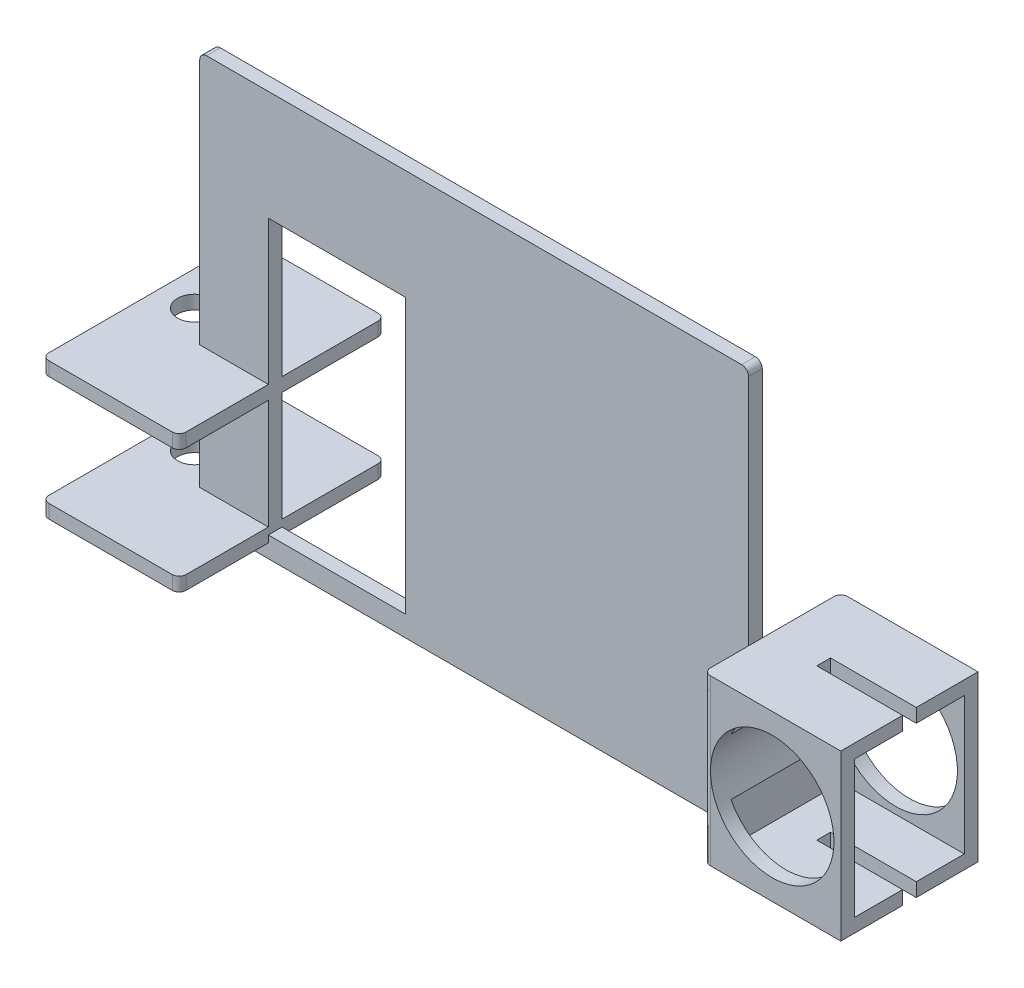
SolidWorks part; units mm, degrees
ref_plane "Front Plane" through (0, 0, 0) normal (0, 0, 1) x (1, 0, 0)
ref_plane "Top Plane" through (0, 0, 0) normal (0, 1, 0) x (1, 0, 0)
ref_plane "Right Plane" through (0, 0, 0) normal (1, 0, 0) x (0, 0, -1)
sketch "Sketch1" plane through (0, 0, 0) normal (0, 1, 0) x (1, 0, 0)
  line L0 (-2.2917, 11.0417) -> (-22.2917, 11.0417)
  line L1 (-22.2917, 11.0417) -> (-22.2917, -8.9583)
  line L2 (-22.2917, -8.9583) -> (-2.2917, -8.9583)
  line L3 (-20.2917, 9.0417) -> (-2.2917, 9.0417)
  line L4 (-20.2917, 9.0417) -> (-20.2917, -6.9583)
  line L5 (-20.2917, -6.9583) -> (-2.2917, -6.9583)
  line L6 (-2.2917, -6.9583) -> (-2.2917, -8.9583)
  line L7 (-2.2917, 9.0417) -> (-2.2917, 11.0417)
  dimension "D1" = 20
  dimension "D2" = 20
  dimension "D3" = 20
  dimension "D4" = 2
  dimension "D5" = 2
  dimension "D6" = 2
extrude "Boss-Extrude1" add sketch "Sketch1" along normal blind 20
fillet "Fillet1" radius 1 2 edges at (-22.2917, 10, -11.0417) (-22.2917, 10, 8.9583)
sketch "Sketch2" plane through (0, 0, 8.9583) normal (0, 0, 1) x (1, 0, 0)
  line L0 (-21.2917, 0) -> (-2.2917, 0) construction
  line L1 (-2.2917, 20) -> (-2.2917, 0) construction
  circle A0 centre (-12.2917, 10) radius 9
  dimension "D3" = 18
  dimension "D1" = 10
  dimension "D2" = 10
extrude "Cut-Extrude1" cut sketch "Sketch2" against normal blind 20
sketch "Sketch3" plane through (0, 20, 0) normal (0, 1, 0) x (1, 0, 0)
  line L0 (-21.2917, 11.0417) -> (-2.2917, 11.0417)
  line L1 (-2.2917, 11.0417) -> (-2.2917, -8.9583)
  line L2 (-2.2917, -8.9583) -> (-22.2917, -8.9583)
  line L3 (-22.2917, -8.9583) -> (-22.2917, 11.0417)
  line L4 (-22.2917, 11.0417) -> (-21.2917, 11.0417)
  line L9 (-2.2917, 2.3778) -> (-2.2917, 0.3778)
  line M10 (-2.2917, 11.0417) -> (-21.2917, 11.0417)
  arc M11 (-21.2917, 11.0417) -> (-22.2917, 10.0417) centre (-21.2917, 10.0417) ccw
  line M12 (-22.2917, 10.0417) -> (-22.2917, -7.9583)
  arc M13 (-22.2917, -7.9583) -> (-21.2917, -8.9583) centre (-21.2917, -7.9583) ccw
  line M14 (-21.2917, -8.9583) -> (-2.2917, -8.9583)
  line M15 (-2.2917, -8.9583) -> (-2.2917, -6.9583)
  line M16 (-2.2917, -6.9583) -> (-20.2917, -6.9583)
  line M17 (-20.2917, -6.9583) -> (-20.2917, 9.0417)
  line M18 (-20.2917, 9.0417) -> (-2.2917, 9.0417)
  line M19 (-2.2917, 9.0417) -> (-2.2917, 11.0417)
  dimension "D1" = 20
extrude "Boss-Extrude2" add sketch "Sketch3" along normal blind 2 contours L1 M18 M17 M16 | M19 M10 M11 M12 M13 M14 M15 M16 M17 M18 region at (-11.7917, 20, -10.7588) region at (-11.2917, 20, -1.0417)
sketch "Sketch4" plane through (0, 0, 0) normal (0, -1, 0) x (1, 0, 0)
  line L0 (-2.2917, 8.9583) -> (-2.2917, -11.0417)
  line L1 (-2.2917, -11.0417) -> (-22.2917, -11.0417)
  line L2 (-22.2917, -11.0417) -> (-22.2917, 8.9583)
  line L3 (-22.2917, 8.9583) -> (-2.2917, 8.9583)
  dimension "D1" = 20
  dimension "D2" = 20
extrude "Boss-Extrude3" add sketch "Sketch4" along normal blind 2
fillet "Fillet2" radius 1 2 edges at (-22.2917, -1, -11.0417) (-22.2917, -1, 8.9583)
sketch "Sketch5" plane through (0, 22, 0) normal (0, 1, 0) x (1, 0, 0)
  line L0 (-2.2917, 11.0417) -> (-2.2917, -8.9583) construction
  line L1 (-14.7917, 2.0417) -> (-2.2917, 2.0417)
  line L2 (-14.7917, 2.0417) -> (-14.7917, 0.0417)
  line L3 (-14.7917, 0.0417) -> (-2.2917, 0.0417)
  line L4 (-2.2917, 2.0417) -> (-2.2917, 0.0417)
  line L5 (-21.2917, -8.9583) -> (-2.2917, -8.9583) construction
  dimension "D1" = 12.5
  dimension "D2" = 2
  dimension "D3" = 9
extrude "Cut-Extrude2" cut sketch "Sketch5" against normal blind 24
sketch "Sketch6" plane through (-22.2917, 0, 0) normal (-1, 0, 0) x (0, 0, 1)
  line L0 (2.4083, -37) -> (0.4083, -37)
  line L5 (0.4083, -37) -> (0.4083, -2)
  line L6 (-10.0417, 22) -> (7.9583, 22) construction
  line L7 (2.4083, 22) -> (0.4083, 22)
  line L8 (2.4083, 22) -> (2.4083, -2)
  line L10 (0.4083, 22) -> (0.4083, -2)
  line L11 (7.9583, -2) -> (-10.0417, -2) construction
  line L13 (2.4083, -2) -> (2.4083, -37)
  line L14 (8.9583, 22) -> (8.9583, 10) construction
  point P6 (1.4083, -37)
  dimension "D1" = 6.55
  dimension "D2" = 2
  dimension "D3" = 35
extrude "Boss-Extrude4" add sketch "Sketch6" along normal blind 80
fillet "Fillet3" radius 1 3 edges at (-22.2917, -37, 1.4083) (-102.2917, -37, 1.4083) (-102.2917, 22, 1.4083)
sketch "Sketch8" plane through (0, 0, 0.4083) normal (0, 0, -1) x (-1, 0, 0)
  line L0 (82.2917, 22) -> (82.2917, -40.0805) construction
  line L1 (72.2917, 19) -> (92.2917, 19)
  line L2 (72.2917, 19) -> (72.2917, -21)
  line L3 (72.2917, -21) -> (92.2917, -21)
  line L4 (92.2917, 19) -> (92.2917, -21)
  line L5 (101.2917, 22) -> (22.2917, 22) construction
  line L6 (12.2917, 10) -> (131.172, 10) construction
  circle A0 centre (12.2917, 10) radius 9 construction
  circle A1 centre (12.2917, 10) radius 7.1139
  dimension "D4" = 70
  dimension "D1" = 20
  dimension "D2" = 40
  dimension "D3" = 10
  dimension "D5" = 9
extrude "Cut-Extrude3" cut sketch "Sketch8" against normal blind 2
sketch "Sketch9" plane through (0, 0, 0.4083) normal (0, 0, -1) x (-1, 0, 0)
  line L0 (92.471, 20) -> (102.2917, 20)
  line L1 (102.2917, 21) -> (102.2917, -36) construction
  line L3 (102.2917, 18) -> (92.2917, 18)
  line L4 (92.2917, -21) -> (92.2917, 19) construction
  line L5 (92.471, 20) -> (92.2917, 20)
  line L6 (92.2917, 20) -> (92.2917, 18)
  line L7 (92.2917, 2) -> (112.2917, 2)
  line L8 (112.2917, 2) -> (112.2917, 0)
  line L9 (112.2917, 0) -> (92.2917, 0)
  line L10 (92.2917, 0) -> (92.2917, 2)
  line L11 (102.2917, 20) -> (112.2917, 20)
  line L12 (112.2917, 20) -> (112.2917, 18)
  line L13 (112.2917, 18) -> (102.2917, 18)
  line L14 (101.2917, 22) -> (22.2917, 22) construction
  point P11 (97.2917, 18)
  dimension "D1" = 2
  dimension "D2" = 2
  dimension "D3" = 16
  dimension "D4" = 20
  dimension "D5" = 20
  dimension "D6" = 2
extrude "Boss-Extrude5" add sketch "Sketch9" along normal mid plane 30
fillet "Fillet4" radius 1 8 edges at (-112.2917, 19, -14.5917) (-112.2917, 1, 15.4083) (-112.2917, 19, 15.4083) (-112.2917, 1, -14.5917) (-92.2917, 1, 15.4083) (-92.2917, 19, 15.4083) (-92.2917, 19, -14.5917) (-92.2917, 1, -14.5917)
sketch "Sketch10" plane through (0, 0, 0) normal (0, -1, 0) x (1, 0, 0)
  line L1 (-92.2917, 0.4083) -> (-102.2917, 0.4083) construction
  line L4 (-102.2917, 0.4083) -> (-102.2917, -14.5917) construction
  line L5 (-93.2917, -14.5917) -> (-111.2917, -14.5917) construction
  line L6 (-107.2917, -17.4424) -> (-107.2917, 10.1065) construction
  circle A0 centre (-107.2917, -1.8487) radius 2.5
  circle A1 centre (-107.2917, -9.8487) radius 2.5
  point P24 (-107.2917, -16.5416)
  dimension "D4" = 5
  dimension "D5" = 5
  dimension "D3" = 5
  dimension "D6" = 8
  dimension "D9" = 5
extrude "Cut-Extrude4" cut sketch "Sketch10" against normal blind 20
mirror "Mirror1" about plane through (0, 22, 0) normal (0, 1, 0) of bodies 109
sketch "Sketch11" plane through (-102.2917, 0, 0) normal (-1, 0, 0) x (0, 0, 1)
  line L0 (0.4083, 22) -> (17.6685, 22)
  line L1 (0.4083, 46) -> (0.4083, -2) construction
  line L2 (17.6685, 22) -> (17.6685, -41.8763)
  line L3 (17.6685, -41.8763) -> (-35.1698, -41.8763)
  line L4 (-35.1698, -41.8763) -> (-35.1698, 22)
  line L5 (-35.1698, 22) -> (0.4083, 22)
extrude "Cut-Extrude5" cut sketch "Sketch11" against normal blind 1000
sketch "Sketch12" plane through (-112.2917, 0, 0) normal (-1, 0, 0) x (0, 0, 1)
  line L1 (-18.3632, 20.9649) -> (19.6889, 20.9649)
  line L2 (-18.3632, 20.9649) -> (-18.3632, -3.7245)
  line L3 (-18.3632, -3.7245) -> (19.6889, -3.7245)
  line L4 (19.6889, 20.9649) -> (19.6889, -3.7245)
extrude "Cut-Extrude6" cut sketch "Sketch12" against normal blind 200
